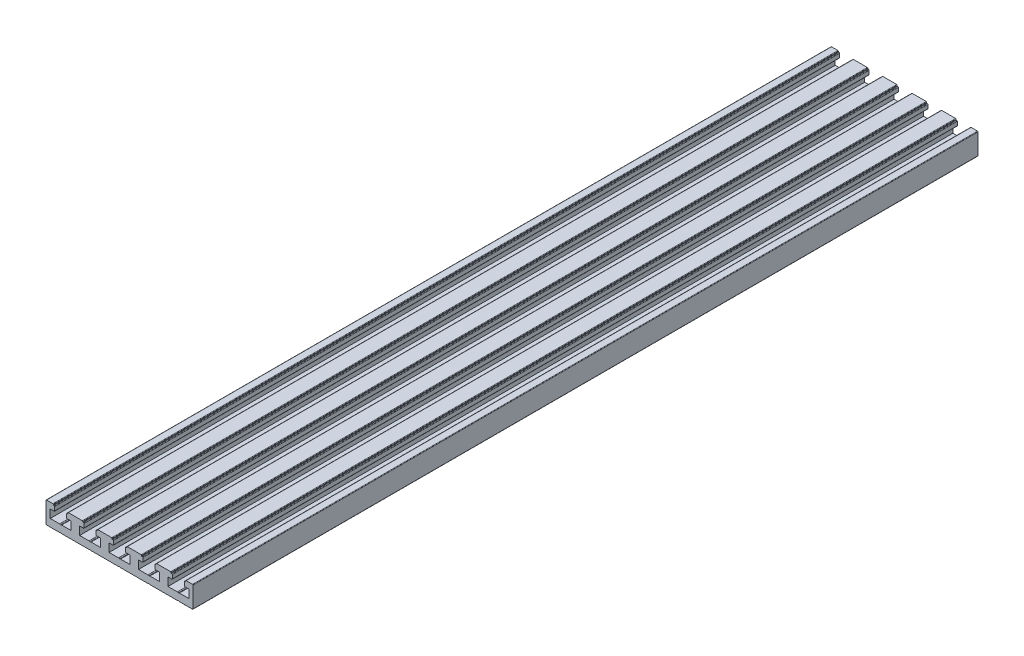
SolidWorks part; units mm, degrees
material "6061-T6 (SS)"
ref_plane "Front Plane" through (0, 0, 0) normal (0, 0, 1) x (1, 0, 0)
ref_plane "Top Plane" through (0, 0, 0) normal (0, 1, 0) x (1, 0, 0)
ref_plane "Right Plane" through (0, 0, 0) normal (1, 0, 0) x (0, 0, -1)
sketch "Sketch1" plane through (0, 0, 0) normal (0, 0, -1) x (-1, 0, 0)
  line L0 (0, 1.72) -> (0, -1.72) construction
  line L1 (-37.45, 8.85) -> (-37.45, -1.65)
  line L2 (-37.2, -1.9) -> (-30.5436, -1.9)
  line L3 (-30.4589, -1.8852) -> (-30, -1.72)
  line L4 (-30, -1.72) -> (-29.5411, -1.8852)
  line L5 (-29.4564, -1.9) -> (-15.5436, -1.9)
  line L6 (-15.4589, -1.8852) -> (-15, -1.72)
  line L7 (-15, -1.72) -> (-14.5411, -1.8852)
  line L8 (-14.4564, -1.9) -> (-0.5436, -1.9)
  line L9 (-0.4589, -1.8852) -> (0, -1.72)
  line L10 (0, -1.72) -> (0.4589, -1.8852)
  line L11 (0.5436, -1.9) -> (14.4564, -1.9)
  line L12 (14.5411, -1.8852) -> (15, -1.72)
  line L13 (15, -1.72) -> (15.4589, -1.8852)
  line L14 (15.5436, -1.9) -> (29.4564, -1.9)
  line L15 (29.5411, -1.8852) -> (30, -1.72)
  line L16 (30, -1.72) -> (30.4589, -1.8852)
  line L17 (30.5436, -1.9) -> (37.2, -1.9)
  line L18 (37.45, -1.65) -> (37.45, 8.85)
  line L19 (37.2, 9.1) -> (33.95, 9.1)
  line L20 (33.7, 8.85) -> (33.7, 8.5)
  line L21 (33.7, 8.5) -> (33.32, 8.5)
  line L22 (33.07, 8.25) -> (33.07, 6.35)
  line L23 (33.32, 6.1) -> (35.3, 6.1)
  line L24 (35.3, 6.1) -> (35.3, 1.9)
  line L25 (35.3, 1.9) -> (30.5436, 1.9)
  line L26 (30.4589, 1.8852) -> (30, 1.72)
  line L27 (30, 1.72) -> (29.5411, 1.8852)
  line L28 (29.4564, 1.9) -> (24.7, 1.9)
  line L29 (24.7, 1.9) -> (24.7, 6.1)
  line L30 (24.7, 6.1) -> (26.68, 6.1)
  line L31 (26.93, 6.35) -> (26.93, 8.25)
  line L32 (26.68, 8.5) -> (26.3, 8.5)
  line L33 (26.3, 8.5) -> (26.3, 8.85)
  line L34 (26.05, 9.1) -> (18.95, 9.1)
  line L35 (18.7, 8.85) -> (18.7, 8.5)
  line L36 (18.7, 8.5) -> (18.32, 8.5)
  line L37 (18.07, 8.25) -> (18.07, 6.35)
  line L38 (18.32, 6.1) -> (20.3, 6.1)
  line L39 (20.3, 6.1) -> (20.3, 1.9)
  line L40 (20.3, 1.9) -> (15.5436, 1.9)
  line L41 (15.4589, 1.8852) -> (15, 1.72)
  line L42 (15, 1.72) -> (14.5411, 1.8852)
  line L43 (14.4564, 1.9) -> (9.7, 1.9)
  line L44 (9.7, 1.9) -> (9.7, 6.1)
  line L45 (9.7, 6.1) -> (11.68, 6.1)
  line L46 (11.93, 6.35) -> (11.93, 8.25)
  line L47 (11.68, 8.5) -> (11.3, 8.5)
  line L48 (11.3, 8.5) -> (11.3, 8.85)
  line L49 (11.05, 9.1) -> (3.95, 9.1)
  line L50 (3.7, 8.85) -> (3.7, 8.5)
  line L51 (3.7, 8.5) -> (3.32, 8.5)
  line L52 (3.07, 8.25) -> (3.07, 6.35)
  line L53 (3.32, 6.1) -> (5.3, 6.1)
  line L54 (5.3, 6.1) -> (5.3, 1.9)
  line L55 (5.3, 1.9) -> (0.5436, 1.9)
  line L56 (0.4589, 1.8852) -> (0, 1.72)
  line L57 (0, 1.72) -> (-0.4589, 1.8852)
  line L58 (-0.5436, 1.9) -> (-5.3, 1.9)
  line L59 (-5.3, 1.9) -> (-5.3, 6.1)
  line L60 (-5.3, 6.1) -> (-3.32, 6.1)
  line L61 (-3.07, 6.35) -> (-3.07, 8.25)
  line L62 (-3.32, 8.5) -> (-3.7, 8.5)
  line L63 (-3.7, 8.5) -> (-3.7, 8.85)
  line L64 (-3.95, 9.1) -> (-11.05, 9.1)
  line L65 (-11.3, 8.85) -> (-11.3, 8.5)
  line L66 (-11.3, 8.5) -> (-11.68, 8.5)
  line L67 (-11.93, 8.25) -> (-11.93, 6.35)
  line L68 (-11.68, 6.1) -> (-9.7, 6.1)
  line L69 (-9.7, 6.1) -> (-9.7, 1.9)
  line L70 (-9.7, 1.9) -> (-14.4564, 1.9)
  line L71 (-14.5411, 1.8852) -> (-15, 1.72)
  line L72 (-15, 1.72) -> (-15.4589, 1.8852)
  line L73 (-15.5436, 1.9) -> (-20.3, 1.9)
  line L74 (-20.3, 1.9) -> (-20.3, 6.1)
  line L75 (-20.3, 6.1) -> (-18.32, 6.1)
  line L76 (-18.07, 6.35) -> (-18.07, 8.25)
  line L77 (-18.32, 8.5) -> (-18.7, 8.5)
  line L78 (-18.7, 8.5) -> (-18.7, 8.85)
  line L79 (-18.95, 9.1) -> (-26.05, 9.1)
  line L80 (-26.3, 8.85) -> (-26.3, 8.5)
  line L81 (-26.3, 8.5) -> (-26.68, 8.5)
  line L82 (-26.93, 8.25) -> (-26.93, 6.35)
  line L83 (-26.68, 6.1) -> (-24.7, 6.1)
  line L84 (-24.7, 6.1) -> (-24.7, 1.9)
  line L85 (-24.7, 1.9) -> (-29.4564, 1.9)
  line L86 (-29.5411, 1.8852) -> (-30, 1.72)
  line L87 (-30, 1.72) -> (-30.4589, 1.8852)
  line L88 (-30.5436, 1.9) -> (-35.3, 1.9)
  line L89 (-35.3, 1.9) -> (-35.3, 6.1)
  line L90 (-35.3, 6.1) -> (-33.32, 6.1)
  line L91 (-33.07, 6.35) -> (-33.07, 8.25)
  line L92 (-33.32, 8.5) -> (-33.7, 8.5)
  line L93 (-33.7, 8.5) -> (-33.7, 8.85)
  line L94 (-33.95, 9.1) -> (-37.2, 9.1)
  arc A0 (-37.45, -1.65) -> (-37.2, -1.9) centre (-37.2, -1.65) ccw
  arc A1 (-30.5436, -1.9) -> (-30.4589, -1.8852) centre (-30.5436, -1.65) ccw
  arc A2 (-29.5411, -1.8852) -> (-29.4564, -1.9) centre (-29.4564, -1.65) ccw
  arc A3 (-15.5436, -1.9) -> (-15.4589, -1.8852) centre (-15.5436, -1.65) ccw
  arc A4 (-14.5411, -1.8852) -> (-14.4564, -1.9) centre (-14.4564, -1.65) ccw
  arc A5 (-0.5436, -1.9) -> (-0.4589, -1.8852) centre (-0.5436, -1.65) ccw
  arc A6 (0.4589, -1.8852) -> (0.5436, -1.9) centre (0.5436, -1.65) ccw
  arc A7 (14.4564, -1.9) -> (14.5411, -1.8852) centre (14.4564, -1.65) ccw
  arc A8 (15.4589, -1.8852) -> (15.5436, -1.9) centre (15.5436, -1.65) ccw
  arc A9 (29.4564, -1.9) -> (29.5411, -1.8852) centre (29.4564, -1.65) ccw
  arc A10 (30.4589, -1.8852) -> (30.5436, -1.9) centre (30.5436, -1.65) ccw
  arc A11 (37.2, -1.9) -> (37.45, -1.65) centre (37.2, -1.65) ccw
  arc A12 (37.45, 8.85) -> (37.2, 9.1) centre (37.2, 8.85) ccw
  arc A13 (33.95, 9.1) -> (33.7, 8.85) centre (33.95, 8.85) ccw
  arc A14 (33.32, 8.5) -> (33.07, 8.25) centre (33.32, 8.25) ccw
  arc A15 (33.07, 6.35) -> (33.32, 6.1) centre (33.32, 6.35) ccw
  arc A16 (30.5436, 1.9) -> (30.4589, 1.8852) centre (30.5436, 1.65) ccw
  arc A17 (29.5411, 1.8852) -> (29.4564, 1.9) centre (29.4564, 1.65) ccw
  arc A18 (26.68, 6.1) -> (26.93, 6.35) centre (26.68, 6.35) ccw
  arc A19 (26.93, 8.25) -> (26.68, 8.5) centre (26.68, 8.25) ccw
  arc A20 (26.3, 8.85) -> (26.05, 9.1) centre (26.05, 8.85) ccw
  arc A21 (18.95, 9.1) -> (18.7, 8.85) centre (18.95, 8.85) ccw
  arc A22 (18.32, 8.5) -> (18.07, 8.25) centre (18.32, 8.25) ccw
  arc A23 (18.07, 6.35) -> (18.32, 6.1) centre (18.32, 6.35) ccw
  arc A24 (15.5436, 1.9) -> (15.4589, 1.8852) centre (15.5436, 1.65) ccw
  arc A25 (14.5411, 1.8852) -> (14.4564, 1.9) centre (14.4564, 1.65) ccw
  arc A26 (11.68, 6.1) -> (11.93, 6.35) centre (11.68, 6.35) ccw
  arc A27 (11.93, 8.25) -> (11.68, 8.5) centre (11.68, 8.25) ccw
  arc A28 (11.3, 8.85) -> (11.05, 9.1) centre (11.05, 8.85) ccw
  arc A29 (3.95, 9.1) -> (3.7, 8.85) centre (3.95, 8.85) ccw
  arc A30 (3.32, 8.5) -> (3.07, 8.25) centre (3.32, 8.25) ccw
  arc A31 (3.07, 6.35) -> (3.32, 6.1) centre (3.32, 6.35) ccw
  arc A32 (0.5436, 1.9) -> (0.4589, 1.8852) centre (0.5436, 1.65) ccw
  arc A33 (-0.4589, 1.8852) -> (-0.5436, 1.9) centre (-0.5436, 1.65) ccw
  arc A34 (-3.32, 6.1) -> (-3.07, 6.35) centre (-3.32, 6.35) ccw
  arc A35 (-3.07, 8.25) -> (-3.32, 8.5) centre (-3.32, 8.25) ccw
  arc A36 (-3.7, 8.85) -> (-3.95, 9.1) centre (-3.95, 8.85) ccw
  arc A37 (-11.05, 9.1) -> (-11.3, 8.85) centre (-11.05, 8.85) ccw
  arc A38 (-11.68, 8.5) -> (-11.93, 8.25) centre (-11.68, 8.25) ccw
  arc A39 (-11.93, 6.35) -> (-11.68, 6.1) centre (-11.68, 6.35) ccw
  arc A40 (-14.4564, 1.9) -> (-14.5411, 1.8852) centre (-14.4564, 1.65) ccw
  arc A41 (-15.4589, 1.8852) -> (-15.5436, 1.9) centre (-15.5436, 1.65) ccw
  arc A42 (-18.32, 6.1) -> (-18.07, 6.35) centre (-18.32, 6.35) ccw
  arc A43 (-18.07, 8.25) -> (-18.32, 8.5) centre (-18.32, 8.25) ccw
  arc A44 (-18.7, 8.85) -> (-18.95, 9.1) centre (-18.95, 8.85) ccw
  arc A45 (-26.05, 9.1) -> (-26.3, 8.85) centre (-26.05, 8.85) ccw
  arc A46 (-26.68, 8.5) -> (-26.93, 8.25) centre (-26.68, 8.25) ccw
  arc A47 (-26.93, 6.35) -> (-26.68, 6.1) centre (-26.68, 6.35) ccw
  arc A48 (-29.4564, 1.9) -> (-29.5411, 1.8852) centre (-29.4564, 1.65) ccw
  arc A49 (-30.4589, 1.8852) -> (-30.5436, 1.9) centre (-30.5436, 1.65) ccw
  arc A50 (-33.32, 6.1) -> (-33.07, 6.35) centre (-33.32, 6.35) ccw
  arc A51 (-33.07, 8.25) -> (-33.32, 8.5) centre (-33.32, 8.25) ccw
  arc A52 (-33.7, 8.85) -> (-33.95, 9.1) centre (-33.95, 8.85) ccw
  arc A53 (-37.2, 9.1) -> (-37.45, 8.85) centre (-37.2, 8.85) ccw
  point P2 (0, 0)
  dimension "D1" = 11
  dimension "D2" = 74.9
extrude "RawPart" add sketch "Sketch1" against normal blind 400
hole_wizard "CSK for M3 Flat Head Machine Screw1" positions "3DSketch1" profile "Sketch2" countersink size "M3" standard "ANSI Metric" end condition through all
sketch3d "3DSketch1"
  point P0 (-30, 1.9, 65)
  point P2 (30, 1.9, 65)
  point P35 (30, 1.9, 330)
  point P37 (-30, 1.9, 330)
  dimension "D4" = 330
  dimension "D1" = 65
  dimension "D2" = 7.45
  dimension "D3" = 60
sketch "Sketch2" plane through (-30, 1.9, 65) normal (1, 0, 0) x (0, 0, 1)
  line L0 (0, 0) -> (0, 3.8)
  line L1 (0, 3.8) -> (1.6, 3.8)
  line L2 (1.6, 3.8) -> (1.6, 1.9)
  line L3 (1.6, 1.9) -> (3, 0.5)
  line L4 (3, 0.5) -> (3, 0)
  line L6 (3, 0) -> (0, 0)
  line L7 (-1.6, 1.9) -> (-3, 0.5) construction
  line L11 (0, -6.35) -> (0, 107.95) construction
  dimension "Thru Hole Dia." = 3.2
  dimension "Thru Hole Depth" = 3.8
  dimension "C'Sink Dia." = 6
  dimension "C'Sink Angle" = 90
  dimension "Head Clearance" = 0.5
hole_wizard "M4x0.7 Tapped Hole1" positions "Sketch4" profile "Sketch5" tap size "M4x0.7" standard "ANSI Metric" end condition through all
sketch "Sketch4" plane through (0, 1.9, 0) normal (0, 1, 0) x (1, 0, 0)
  line L1 (-0.5436, 0) -> (-14.4564, 0) construction
  line L2 (-37.45, -400) -> (-37.45, 0) construction
  line L3 (15, -400) -> (15, 0) construction
  line L5 (-26.05, 0) -> (-18.95, 0) construction
  point P0 (15, -30)
  point P15 (15, -372)
  dimension "D1" = 30
  dimension "D2" = 52.45
  dimension "D3" = 372
sketch "Sketch5" plane through (15, 1.9, 30) normal (1, 0, 0) x (0, 0, 1)
  line L0 (0, 0) -> (0, 3.8)
  line L1 (0, 3.8) -> (1.65, 3.8)
  line L2 (1.65, 3.8) -> (1.65, 0)
  line L5 (1.65, 0) -> (0, 0)
  line L11 (0, -6.35) -> (0, 107.95) construction
  dimension "Thru Tap Drill Dia." = 3.3
  dimension "Thru Tap Drill Depth" = 3.8
cosmetic thread "Hole Thread4" parameters "D2"=4
cosmetic thread "Hole Thread10" parameters "D2"=4
sketch "Sketch6" [suppressed] plane through (0, 0, 0) normal (0, 0, -1) x (-1, 0, 0)
  line L0 (37.45, -1.65) -> (37.45, 8.85) construction
  line L1 (-14.55, -9.9057) -> (-41.3993, -9.9057)
  line L2 (-14.55, -9.9057) -> (-14.55, 14.5956)
  line L3 (-14.55, 14.5956) -> (-41.3993, 14.5956)
  line L4 (-41.3993, -9.9057) -> (-41.3993, 14.5956)
  dimension "D1" = 52
extrude "CutUnnecessaryHalf" [suppressed] cut sketch "Sketch6" against normal through all
equation "\"D4@3DSketch1\" = \"D1@RawPart\" - \"D1@3DSketch1\" - 5"
